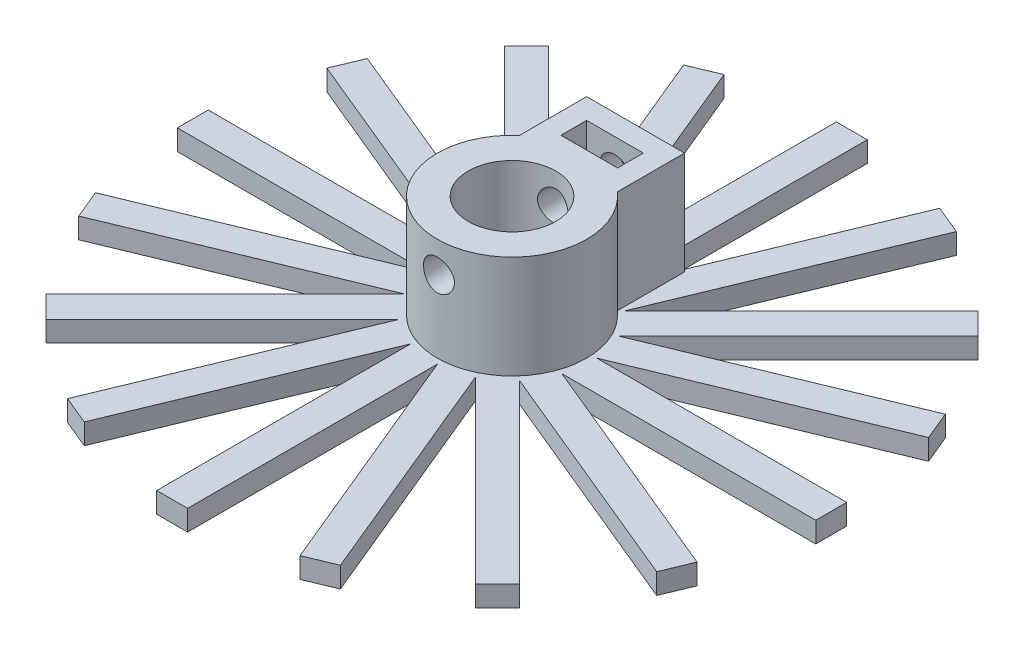
SolidWorks part; units mm, degrees
ref_plane "Front Plane" through (0, 0, 0) normal (0, 0, 1) x (1, 0, 0)
ref_plane "Top Plane" through (0, 0, 0) normal (0, 1, 0) x (1, 0, 0)
ref_plane "Right Plane" through (0, 0, 0) normal (1, 0, 0) x (0, 0, -1)
sketch "Sketch1" plane through (0, 0, 0) normal (0, 1, 0) x (1, 0, 0)
  line L0 (-0.4619, 0.1913) -> (11.7839, 29.7555)
  line L1 (-0.5, 0) -> (2.5, 0)
  line L2 (-0.5, 0) -> (-0.5, 32)
  line L3 (-0.5, 32) -> (2.5, 32)
  line L4 (2.5, 0) -> (2.5, 32)
  line L5 (-0.4619, 0.1913) -> (2.3097, -0.9567)
  line L6 (2.3097, -0.9567) -> (14.5556, 28.6074)
  line L7 (11.7839, 29.7555) -> (14.5556, 28.6074)
  line L8 (-0.3536, 0.3536) -> (22.2739, 22.981)
  line L9 (-0.3536, 0.3536) -> (1.7678, -1.7678)
  line L10 (1.7678, -1.7678) -> (24.3952, 20.8597)
  line L11 (22.2739, 22.981) -> (24.3952, 20.8597)
  line L12 (-0.1913, 0.4619) -> (29.3728, 12.7078)
  line L13 (-0.1913, 0.4619) -> (0.9567, -2.3097)
  line L14 (0.9567, -2.3097) -> (30.5209, 9.9362)
  line L15 (29.3728, 12.7078) -> (30.5209, 9.9362)
  line L16 (0, 0.5) -> (32, 0.5)
  line L17 (0, 0.5) -> (0, -2.5)
  line L18 (0, -2.5) -> (32, -2.5)
  line L19 (32, 0.5) -> (32, -2.5)
  line L20 (0.1913, 0.4619) -> (29.7555, -11.7839)
  line L21 (0.1913, 0.4619) -> (-0.9567, -2.3097)
  line L22 (-0.9567, -2.3097) -> (28.6074, -14.5556)
  line L23 (29.7555, -11.7839) -> (28.6074, -14.5556)
  line L24 (0.3536, 0.3536) -> (22.981, -22.2739)
  line L25 (0.3536, 0.3536) -> (-1.7678, -1.7678)
  line L26 (-1.7678, -1.7678) -> (20.8597, -24.3952)
  line L27 (22.981, -22.2739) -> (20.8597, -24.3952)
  line L28 (0.4619, 0.1913) -> (12.7078, -29.3728)
  line L29 (0.4619, 0.1913) -> (-2.3097, -0.9567)
  line L30 (-2.3097, -0.9567) -> (9.9362, -30.5209)
  line L31 (12.7078, -29.3728) -> (9.9362, -30.5209)
  line L32 (0.5, 0) -> (0.5, -32)
  line L33 (0.5, 0) -> (-2.5, 0)
  line L34 (-2.5, 0) -> (-2.5, -32)
  line L35 (0.5, -32) -> (-2.5, -32)
  line L36 (0.4619, -0.1913) -> (-11.7839, -29.7555)
  line L37 (0.4619, -0.1913) -> (-2.3097, 0.9567)
  line L38 (-2.3097, 0.9567) -> (-14.5556, -28.6074)
  line L39 (-11.7839, -29.7555) -> (-14.5556, -28.6074)
  line L40 (0.3536, -0.3536) -> (-22.2739, -22.981)
  line L41 (0.3536, -0.3536) -> (-1.7678, 1.7678)
  line L42 (-1.7678, 1.7678) -> (-24.3952, -20.8597)
  line L43 (-22.2739, -22.981) -> (-24.3952, -20.8597)
  line L44 (0.1913, -0.4619) -> (-29.3728, -12.7078)
  line L45 (0.1913, -0.4619) -> (-0.9567, 2.3097)
  line L46 (-0.9567, 2.3097) -> (-30.5209, -9.9362)
  line L47 (-29.3728, -12.7078) -> (-30.5209, -9.9362)
  line L48 (0, -0.5) -> (-32, -0.5)
  line L49 (0, -0.5) -> (0, 2.5)
  line L50 (0, 2.5) -> (-32, 2.5)
  line L51 (-32, -0.5) -> (-32, 2.5)
  line L52 (-0.1913, -0.4619) -> (-29.7555, 11.7839)
  line L53 (-0.1913, -0.4619) -> (0.9567, 2.3097)
  line L54 (0.9567, 2.3097) -> (-28.6074, 14.5556)
  line L55 (-29.7555, 11.7839) -> (-28.6074, 14.5556)
  line L56 (-0.3536, -0.3536) -> (-22.981, 22.2739)
  line L57 (-0.3536, -0.3536) -> (1.7678, 1.7678)
  line L58 (1.7678, 1.7678) -> (-20.8597, 24.3952)
  line L59 (-22.981, 22.2739) -> (-20.8597, 24.3952)
  line L60 (-0.4619, -0.1913) -> (-12.7078, 29.3728)
  line L61 (-0.4619, -0.1913) -> (2.3097, 0.9567)
  line L62 (2.3097, 0.9567) -> (-9.9362, 30.5209)
  line L63 (-12.7078, 29.3728) -> (-9.9362, 30.5209)
  circle A0 centre (0, 0) radius 4.25
  circle A1 centre (0, 0) radius 7.25
  point P39 (0, 0)
  dimension "D1" = 8.5
  dimension "D4" = 3
  dimension "D2" = 3
  dimension "D3" = 2.5
  dimension "D5" = 32
  dimension "D6" = 32
  dimension "D7" = 16
extrude "Boss-Extrude1" add sketch "Sketch1" along normal blind 2 contours L50 L51 L48 L49 | L54 L55 L52 L53 | L58 L59 L56 L57 | L62 L63 L60 L61 | L4 L3 L2 L1 | L6 L7 L0 L5 | L10 L11 L8 L9 | L14 L15 L12 L13 | L18 L19 L16 L17 | L22 L23 L20 L21 | L26 L27 L24 L25 | L30 L31 L28 L29 | L34 L35 L32 L33 | L38 L39 L36 L37 | L42 L43 L40 L41 | L46 L47 L44 L45 | A1 | A0
extrude "Boss-Extrude2" add sketch "Sketch1<3>" along normal blind 12 contours A1 | A0
sketch "Sketch1<3>" plane through (0, 0, 0) normal (0, 1, 0) x (1, 0, 0) same geometry as "Sketch1"
sketch "Sketch5" plane through (0, 12, 0) normal (0, 1, 0) x (1, 0, 0)
  line L1 (-2.75, 10) -> (2.75, 10)
  line L2 (-2.75, 10) -> (-2.75, 7.5)
  line L3 (-2.75, 7.5) -> (2.75, 7.5)
  line L4 (2.75, 10) -> (2.75, 7.5)
  line L5 (4.75, 12) -> (-4.75, 12)
  line L6 (4.75, 12) -> (4.75, 5.5)
  line L7 (4.75, 5.5) -> (-4.75, 5.5)
  line L8 (-4.75, 12) -> (-4.75, 5.5)
  circle A1 centre (0, 0) radius 7.25 construction
  point P10 (0, 10)
  dimension "D6" = 0
  dimension "D1" = 2.5
  dimension "D2" = 5.5
  dimension "D3" = 2
  dimension "D4" = 2
  dimension "D5" = 2
  dimension "D7" = 7.5
  dimension "D8" = 2
extrude "Boss-Extrude3" add sketch "Sketch5" against normal blind 10
sketch "Sketch2" plane through (0, 0, 0) normal (0, 0, 1) x (1, 0, 0)
  line L0 (7.25, 12) -> (-7.25, 12) construction
  circle A0 centre (0, 9) radius 1.5
  dimension "D1" = 3
  dimension "D2" = 3
extrude "Cut-Extrude1" cut sketch "Sketch2" against normal through all both and the other way through all
sketch "Sketch3" plane through (0, 12, 0) normal (0, 1, 0) x (1, 0, 0)
  circle A0 centre (0, 0) radius 4.25
extrude "Cut-Extrude3" cut sketch "Sketch3" against normal through all both
